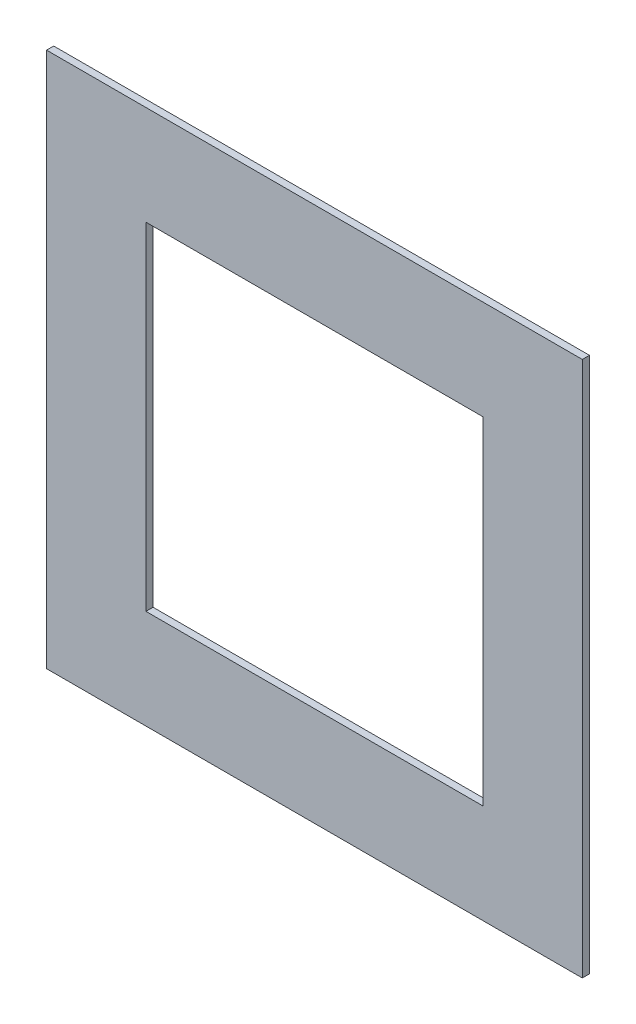
SolidWorks part; units mm, degrees
material "Balsa"
ref_plane "Ebene vorne" through (0, 0, 0) normal (0, 0, 1) x (1, 0, 0)
ref_plane "Ebene oben" through (0, 0, 0) normal (0, 1, 0) x (1, 0, 0)
ref_plane "Ebene rechts" through (0, 0, 0) normal (1, 0, 0) x (0, 0, -1)
sketch "Skizze1" plane through (0, 0, 0) normal (0, 0, 1) x (1, 0, 0)
  line L0 (600, 600) -> (-600, 600)
  line L1 (377.5, -377.5) -> (-377.5, -377.5)
  line L2 (377.5, -377.5) -> (377.5, 377.5)
  line L3 (377.5, 377.5) -> (-377.5, 377.5)
  line L4 (-377.5, -377.5) -> (-377.5, 377.5)
  line L5 (377.5, -377.5) -> (-377.5, 377.5) construction
  line L6 (377.5, 377.5) -> (-377.5, -377.5) construction
  line L11 (-600, -600) -> (-600, 600)
  line L12 (600, -600) -> (-600, -600)
  line L13 (400, -400) -> (-400, -400) construction
  line L14 (400, -400) -> (400, 400) construction
  line L15 (400, 400) -> (-400, 400) construction
  line L16 (-400, -400) -> (-400, 400) construction
  line L17 (400, -400) -> (-400, 400) construction
  line L18 (400, 400) -> (-400, -400) construction
  line L19 (600, -600) -> (600, 600)
  point P0 (0, 0)
  point P6 (0, 0)
  point P11 (0, 0)
  dimension "D1" = 755
  dimension "D2" = 800
  dimension "D3" = 200
extrude "Aufsatz-Linear austragen1" add sketch "Skizze1" along normal blind 16
equation "\"wall_thickness\"= 4mm"
equation "\"wall_height\"= 300"
equation "\"edge_length\"= 800mm"
equation "\"coldplate_circumference\"= 4*\"edge_length\""
equation "\"L-profile_width\"= 20mm"
equation "\"L-profile_thickness\"= 1.5mm"
equation "\"D1@Skizze1\"=\"edge_length\" - \"L-profile_width\"*2 - 5"
equation "\"D2@Skizze1\"=\"edge_length\""
